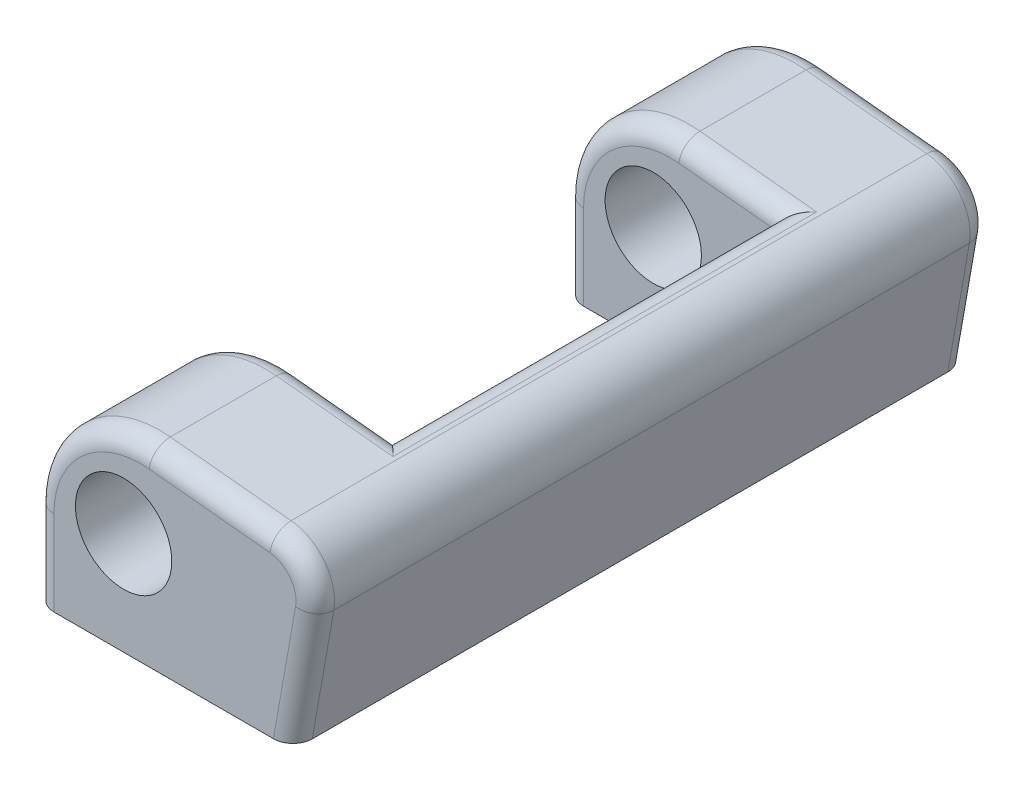
SolidWorks part; units mm, degrees
ref_plane "Front Plane" through (0, 0, 0) normal (0, 0, 1) x (1, 0, 0)
ref_plane "Top Plane" through (0, 0, 0) normal (0, 1, 0) x (1, 0, 0)
ref_plane "Right Plane" through (0, 0, 0) normal (1, 0, 0) x (0, 0, -1)
sketch "Sketch1" plane through (0, 0, 0) normal (0, 0, 1) x (1, 0, 0)
  line L0 (0, 0) -> (0, 8.8451)
  line L1 (12.0945, 19.7905) -> (30, 18)
  line L2 (30, 18) -> (26.8261, 0)
  line L3 (26.8261, 0) -> (0, 0)
  arc A0 (0, 8.8451) -> (12.0945, 19.7905) centre (11, 8.8451) cw
  point P7 (0, 21)
  dimension "D5" = 11
  dimension "D1" = 21
  dimension "D2" = 18
  dimension "D3" = 80
  dimension "D4" = 30
extrude "Boss-Extrude1" add sketch "Sketch1" along normal mid plane 70
sketch "Sketch2" plane through (0, 0, 0) normal (0, 1, 0) x (1, 0, 0)
  line L0 (30, -35) -> (30, 35) construction
  line L1 (-22, 20) -> (22, 20)
  line L2 (-22, 20) -> (-22, -20)
  line L3 (-22, -20) -> (22, -20)
  line L4 (22, 20) -> (22, -20)
  line L5 (-22, 20) -> (22, -20) construction
  line L6 (-22, -20) -> (22, 20) construction
  point P0 (0, 0)
  dimension "D1" = 40
  dimension "D2" = 8
extrude "Cut-Extrude2" cut sketch "Sketch2" along normal through all
fillet "Fillet1" radius 2 15 edges at (0, 4.4226, -35) (3.6189, 17.0011, -35) (0, 4.4226, -20) (3.6189, 17.0011, -20) (0, 4.4226, 35) (0, 4.4226, 20) (21.0473, 18.8953, -35) (21.0473, 18.8953, 35) (17.0473, 19.2953, 20) (22, 18.8, 0) (17.0473, 19.2953, -20) (3.6189, 17.0011, 35) (3.6189, 17.0011, 20) (28.4131, 9, -35) (28.4131, 9, 35)
sketch "Sketch3" plane through (0, 0, 35) normal (0, 0, 1) x (1, 0, 0)
  circle A0 centre (9.2354, 10.6635) radius 5
  dimension "D1" = 10
extrude "Cut-Extrude3" cut sketch "Sketch3" against normal through all
fillet "Fillet2" radius 5 3 edges at (29.3135, 17.4799, -34.4142) (29.3135, 17.4799, 34.4142) (30, 18, 0)
